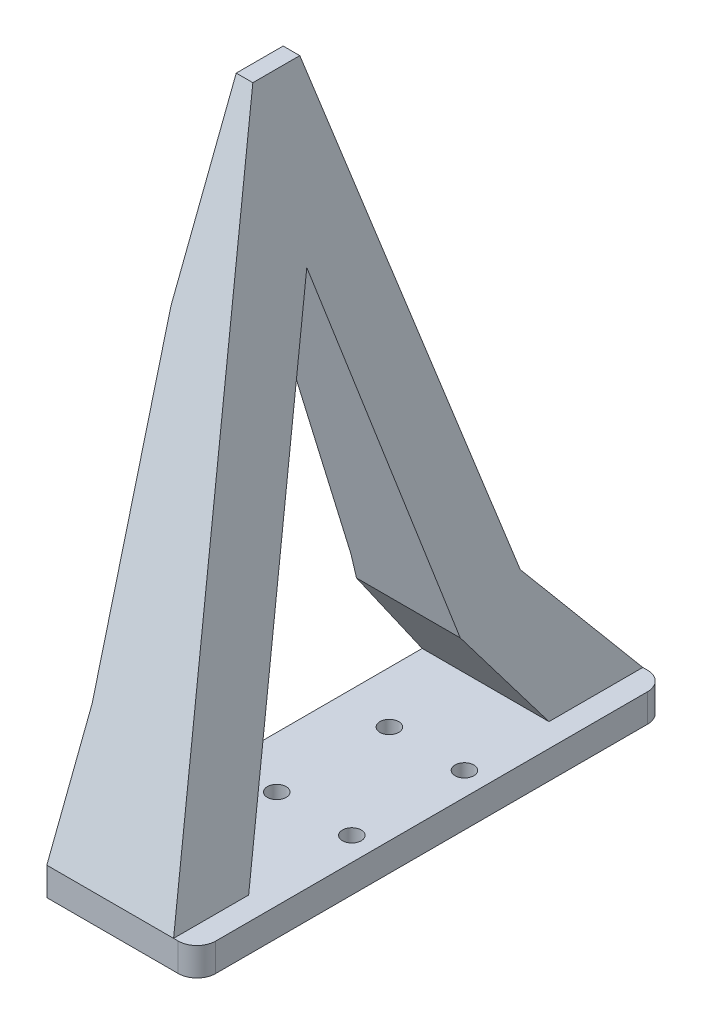
SolidWorks part; units mm, degrees
ref_plane "前视基准面" through (0, 0, 0) normal (0, 0, 1) x (1, 0, 0)
ref_plane "上视基准面" through (0, 0, 0) normal (0, 1, 0) x (1, 0, 0)
ref_plane "右视基准面" through (0, 0, 0) normal (1, 0, 0) x (0, 0, -1)
sketch "草图1" plane through (0, 0, 0) normal (0, 1, 0) x (1, 0, 0)
  line L0 (2.75, 0) -> (0, 0) construction
  line L1 (-9.25, 25) -> (7.25, 25)
  line L2 (-9.25, 25) -> (-9.25, -25)
  line L3 (-9.25, -25) -> (7.25, -25)
  line L4 (9.25, 23) -> (9.25, -23)
  line L5 (-9.25, 25) -> (9.25, -25) construction
  line L6 (-9.25, -25) -> (9.25, 25) construction
  line L7 (-1.25, 6) -> (6.75, 6) construction
  line L8 (-1.25, 6) -> (-1.25, -6) construction
  line L9 (-1.25, -6) -> (6.75, -6) construction
  line L10 (6.75, 6) -> (6.75, -6) construction
  line L11 (-1.25, 6) -> (6.75, -6) construction
  line L12 (-1.25, -6) -> (6.75, 6) construction
  circle A0 centre (-1.25, 6) radius 1
  circle A1 centre (-1.25, -6) radius 1
  circle A2 centre (6.75, -6) radius 1
  circle A3 centre (6.75, 6) radius 1
  arc A5 (7.25, -25) -> (9.25, -23) centre (7.25, -23) ccw
  arc A6 (7.25, 25) -> (9.25, 23) centre (7.25, 23) cw
  point P0 (0, 0)
  point P6 (2.75, 0)
  point P17 (0, 0)
  point P27 (0, 0)
  point P28 (0, 0)
  dimension "D3" = 2
  dimension "D1" = 12
  dimension "D2" = 8
  dimension "D4" = 8
  dimension "D5" = 5
  dimension "D6" = 50
extrude "凸台-拉伸1" add sketch "草图1" along normal blind 3
sketch "草图2" plane through (0, 3, 0) normal (0, 1, 0) x (1, 0, 0)
  line L0 (-9.25, -25) -> (7.25, -25) construction
  line L1 (6.7578, -25) -> (-9.25, -25)
  line L2 (6.7578, -25) -> (6.7578, 25)
  line L3 (6.7578, 25) -> (-9.25, 25)
  line L4 (-9.25, -25) -> (-9.25, 25)
  line L5 (6.7578, -25) -> (-9.25, 25) construction
  line L6 (6.7578, 25) -> (-9.25, -25) construction
  point P0 (-1.2461, 0)
  point P6 (3.2534, -25)
  point P7 (0, 0)
  point P10 (6.7578, -25)
extrude "凸台-拉伸2" add sketch "草图2" along normal blind 80
sketch "草图3" plane through (6.7578, 0, 0) normal (1, 0, 0) x (0, 0, -1)
  line L2 (0, 0) -> (0, 36.8077) construction
  line L4 (0, 47) -> (-17, 3)
  line L5 (-25, 3) -> (-7, 3) construction
  line L6 (25, 3) -> (15, 15.5)
  line L8 (15, 15.5) -> (3.1818, 63)
  line L10 (15, 3) -> (8, 13)
  line L11 (7, 3) -> (25, 3) construction
  line L13 (8, 13) -> (0, 47)
  line L14 (15, 3) -> (-17, 3)
  line L15 (25, 3) -> (63.3284, 3)
  line L16 (63.3284, 3) -> (63.3284, 88.4369)
  line L17 (63.3284, 88.4369) -> (-37.68, 88.4369)
  line L18 (-37.68, 88.4369) -> (-37.68, 3)
  line L19 (-37.68, 3) -> (-25, 3)
  line L20 (-25, 3) -> (-1.8182, 63)
  line L21 (3.1818, 63) -> (-1.8182, 63)
  line L22 (-23, 0) -> (23, 0) construction
  dimension "D1" = 8
  dimension "D2" = 10
  dimension "D3" = 5
  dimension "D4" = 60
  dimension "D5" = 8
  dimension "D6" = 13
  dimension "D7" = 15
  dimension "D8" = 15.5
  dimension "D9" = 47
extrude "切除-拉伸1" cut sketch "草图3" against normal through all
sketch "草图4" plane through (0, 0, -25) normal (0, 0, -1) x (-1, 0, 0)
  line L0 (-6.7578, 3) -> (8.4076, 64.7421)
  line L2 (8.4076, 64.7421) -> (-6.7578, 64.7421)
  line L3 (-6.7578, 64.7421) -> (-6.7578, 3)
  point P3 (0, 0)
  point P4 (8.4609, 64.729)
  point P7 (0, 0)
  dimension "D1" = 103.8
extrude "切除-拉伸2" cut sketch "草图4" against normal through all
sketch "草图5" plane through (-9.25, 0, 0) normal (-1, 0, 0) x (0, 0, 1)
  line L0 (0, 47) -> (-8, 13)
  line L1 (-8, 13) -> (-15, 3)
  line L2 (-15, 3) -> (17, 3)
  line L3 (17, 3) -> (0, 47)
  line L4 (-3.1818, 63) -> (-15, 15.5)
  line L5 (-15, 15.5) -> (-25, 3)
  line L6 (-25, 3) -> (-25, 0)
  line L7 (-25, 0) -> (25, 0)
  line L8 (25, 0) -> (25, 3)
  line L9 (25, 3) -> (1.8182, 63)
  line L10 (1.8182, 63) -> (-3.1818, 63)
extrude "凸台-拉伸3" add sketch "草图5" along normal blind 3
sketch "草图6" plane through (0, 0, -25) normal (0, 0, -1) x (-1, 0, 0)
  line L0 (9.75, 65) -> (9.75, 45)
  line L1 (12.25, 63) -> (12.25, 15.5) construction
  line L2 (9.75, 45) -> (6.75, 15.5)
  line L3 (12.25, 15.5) -> (-3.6875, 15.5) construction
  line L4 (6.75, 15.5) -> (6.75, 0)
  line L5 (-7.25, 0) -> (12.25, 0) construction
  line L6 (6.75, 0) -> (15.0651, 0)
  line L7 (15.0651, 0) -> (15.0651, 65)
  line L8 (15.0651, 65) -> (9.75, 65)
  line L9 (12.25, 63) -> (7.9797, 63) construction
  dimension "D1" = 2.5
  dimension "D2" = 20
  dimension "D3" = 5.5
  dimension "D4" = 18
extrude "切除-拉伸3" cut sketch "草图6" against normal through all
